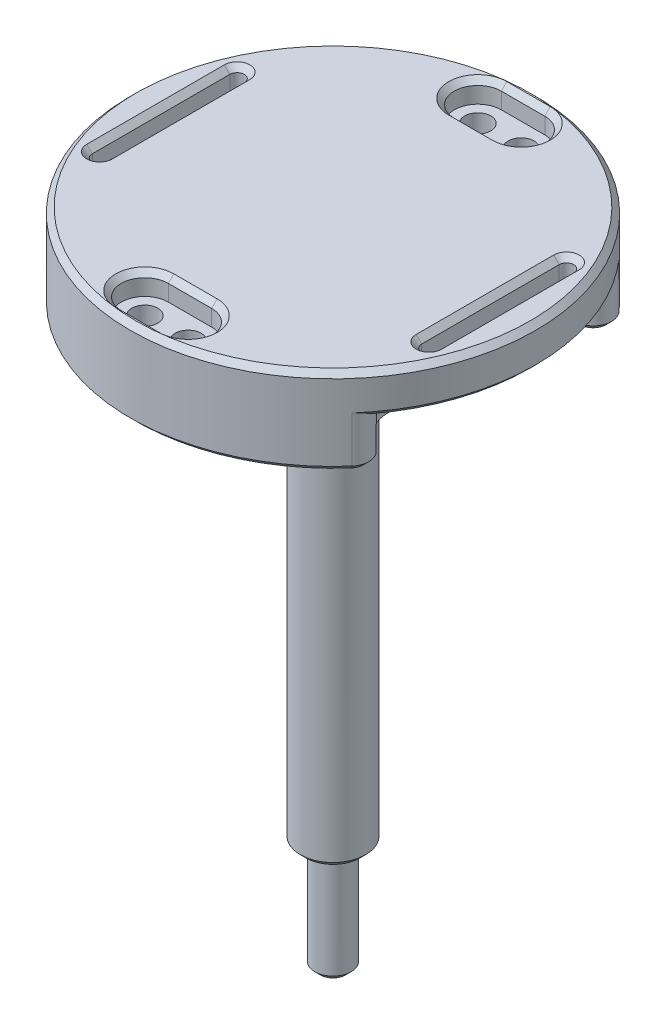
SolidWorks part; units mm, degrees
ref_plane "Front Plane" through (0, 0, 0) normal (0, 0, 1) x (1, 0, 0)
ref_plane "Top Plane" through (0, 0, 0) normal (0, 1, 0) x (1, 0, 0)
ref_plane "Right Plane" through (0, 0, 0) normal (1, 0, 0) x (0, 0, -1)
sketch "Sketch1" plane through (0, 0, 0) normal (0, 0, 1) x (1, 0, 0)
  line L0 (0, 0) -> (0, 91) construction
  line L1 (0, 91) -> (28, 91)
  line L2 (28, 91) -> (28, 79)
  line L3 (28, 79) -> (15, 79)
  line L4 (15, 79) -> (15, 80)
  line L5 (15, 80) -> (4.5, 80)
  line L6 (4.5, 80) -> (4.5, 15)
  line L7 (4.5, 15) -> (2.5, 15)
  line L8 (2.5, 15) -> (2.5, 0)
  line L9 (2.5, 0) -> (0, 0)
  line L10 (0, 0) -> (0, 91)
  dimension "D1" = 79
  dimension "D2" = 5
  dimension "D3" = 9
  dimension "D4" = 1
  dimension "D5" = 30
  dimension "D6" = 12
  dimension "D7" = 56
  dimension "D8" = 15
revolve "Revolve1" add sketch "Sketch1" angle 360 about L0
hole_wizard "CBORE for M3 SHCS1" positions "Sketch2" profile "Sketch3" counterbore size "M3" standard "ANSI Metric" end condition through all
sketch "Sketch2" plane through (0, 91, 0) normal (0, 1, 0) x (1, 0, 0)
  line L0 (0, 0) -> (0, 23) construction
  line L1 (0, 23) -> (3, 23) construction
  line L3 (0, 23) -> (-3, 23) construction
  line L5 (-3, -23) -> (0, -23) construction
  line L6 (0, -23) -> (0, 0) construction
  line L8 (0, -23) -> (3, -23) construction
  point P0 (3, 23)
  point P11 (-3, 23)
  point P14 (-3, -23)
  point P21 (3, -23)
  dimension "D1" = 46
  dimension "D2" = 6
sketch "Sketch3" plane through (3, 91, -23) normal (1, 0, 0) x (0, 0, 1)
  line L0 (0, 0) -> (0, 91)
  line L1 (0, 91) -> (1.8, 91)
  line L3 (1.8, 91) -> (1.8, 3)
  line L4 (1.8, 3) -> (3.25, 3)
  line L5 (3.25, 3) -> (3.25, 0)
  line L7 (3.25, 0) -> (0, 0)
  line L11 (0, -6.35) -> (0, 107.95) construction
  dimension "Thru Hole Dia." = 3.6
  dimension "Thru Hole Depth" = 91
  dimension "C'Bore Dia." = 6.5
  dimension "C'Bore Depth" = 3
sketch "Sketch4" plane through (0, 88, 0) normal (0, 1, 0) x (1, 0, 0)
  line L0 (-3, 23) -> (3, 23) construction
  line L1 (-3, 26.25) -> (3, 26.25)
  line L2 (-3, 19.75) -> (3, 19.75)
  line L3 (-3, -23) -> (3, -23) construction
  line L4 (-3, -19.75) -> (3, -19.75)
  line L5 (-3, -26.25) -> (3, -26.25)
  arc A0 (-3, 26.25) -> (-3, 19.75) centre (-3, 23) ccw
  arc A1 (3, 19.75) -> (3, 26.25) centre (3, 23) ccw
  arc A2 (0, 21.75) -> (0, 24.25) centre (3, 23) ccw construction
  arc A3 (-3, -19.75) -> (-3, -26.25) centre (-3, -23) ccw
  arc A4 (3, -26.25) -> (3, -19.75) centre (3, -23) ccw
  arc A5 (0, -21.75) -> (0, -24.25) centre (-3, -23) ccw construction
  point P4 (0, 23)
  point P16 (0, -23)
extrude "Cut-Extrude1" cut sketch "Sketch4" along normal through all
sketch "Sketch5" plane through (0, 91, 0) normal (0, 1, 0) x (1, 0, 0)
  line L0 (-22.75, -9.5) -> (-22.75, 9.5) construction
  line L1 (-23.75, -9.5) -> (-23.75, 9.5)
  line L2 (-21.75, -9.5) -> (-21.75, 9.5)
  arc A0 (-23.75, -9.5) -> (-21.75, -9.5) centre (-22.75, -9.5) ccw
  arc A1 (-21.75, 9.5) -> (-23.75, 9.5) centre (-22.75, 9.5) ccw
  point P2 (-22.75, 0)
  dimension "D1" = 22.75
  dimension "D2" = 19
  dimension "D3" = 2
extrude "Cut-Extrude2" cut sketch "Sketch5" against normal through all
mirror "Mirror1" about plane through (0, 0, 0) normal (1, 0, 0) of "Cut-Extrude2"
sketch "Sketch7" plane through (0, 79, 0) normal (0, -1, 0) x (1, 0, 0)
  line L0 (21.75, -9.5) -> (21.75, 9.5)
  line L1 (21.75, -9.5) -> (21.75, 9.5) construction
  line L2 (23.75, 9.5) -> (23.75, -9.5)
  line L3 (23.75, 9.5) -> (23.75, -9.5) construction
  line L4 (-21.75, -9.5) -> (-21.75, 9.5)
  line L5 (-21.75, -9.5) -> (-21.75, 9.5) construction
  line L6 (-23.75, 9.5) -> (-23.75, -9.5)
  line L7 (-23.75, 9.5) -> (-23.75, -9.5) construction
  line L8 (28.322, 9.5) -> (28.322, -9.5)
  line L9 (17.178, -9.5) -> (17.178, 9.5)
  line L10 (-17.178, -9.5) -> (-17.178, 9.5)
  line L11 (-28.322, 9.5) -> (-28.322, -9.5)
  arc A0 (23.75, 9.5) -> (21.75, 9.5) centre (22.75, 9.5) ccw
  arc A1 (23.75, 9.5) -> (21.75, 9.5) centre (22.75, 9.5) ccw construction
  arc A2 (21.75, -9.5) -> (23.75, -9.5) centre (22.75, -9.5) ccw
  arc A3 (21.75, -9.5) -> (23.75, -9.5) centre (22.75, -9.5) ccw construction
  arc A4 (-23.75, -9.5) -> (-21.75, -9.5) centre (-22.75, -9.5) ccw
  arc A5 (-23.75, -9.5) -> (-21.75, -9.5) centre (-22.75, -9.5) ccw construction
  arc A6 (-21.75, 9.5) -> (-23.75, 9.5) centre (-22.75, 9.5) ccw
  arc A7 (-21.75, 9.5) -> (-23.75, 9.5) centre (-22.75, 9.5) ccw construction
  arc A8 (17.178, -9.5) -> (28.322, -9.5) centre (22.75, -9.5) ccw
  arc A9 (28.322, 9.5) -> (17.178, 9.5) centre (22.75, 9.5) ccw
  arc A10 (-17.178, 9.5) -> (-28.322, 9.5) centre (-22.75, 9.5) ccw
  arc A11 (-28.322, -9.5) -> (-17.178, -9.5) centre (-22.75, -9.5) ccw
  dimension "D1" = 4.572
  dimension "D2" = 4.572
extrude "Cut-Extrude3" cut sketch "Sketch7" against normal blind 6.35
fillet "Fillet1" radius 2.54 4 edges at (23.6432, 82.175, 14.9999) (23.6432, 82.175, -14.9999) (-23.6432, 82.175, -14.9999) (-23.6432, 82.175, 14.9999)
fillet "Fillet2" radius 1.27 8 edges at (-22.75, 85.35, -10.5) (-21.75, 85.35, 0) (-22.75, 85.35, 10.5) (22.75, 85.35, 10.5) (23.75, 85.35, 0) (22.75, 85.35, -10.5) (-23.75, 85.35, 0) (21.75, 85.35, 0)
chamfer "Chamfer1" distance 0.762 angle 45 38 edges at (0, 79, -15) (3, 79, 21.2) (-3, 79, 21.2) (-3, 79, -24.8) (3, 79, -24.8) (22.75, 91, -10.5) (21.75, 91, 0) (22.75, 91, 10.5) (23.75, 91, 0) (0, 91, -26.25) (-6.25, 91, -23) (0, 91, -19.75) (6.25, 91, -23) (0, 91, 19.75) (-6.25, 91, 23) (0, 91, 26.25) (6.25, 91, 23) (0, 91, -28) (-21.75, 91, 0) (-22.75, 91, -10.5) (-23.75, 91, 0) (-22.75, 91, 10.5) (0, 15, -4.5) (0, 0, -2.5) (17.178, 79, 0) (18.0168, 79, -12.4401) (21.6463, 79, -16.2766) (0, 79, -28) (-21.6463, 79, -16.2766) (-18.0168, 79, -12.4401) (-17.178, 79, 0) (-18.0168, 79, 12.4401) (-21.6463, 79, 16.2766) (0, 79, 28) (21.6463, 79, 16.2766) (18.0168, 79, 12.4401) (-28, 85.35, 0) (28, 85.35, 0)
fillet "Fillet3" radius 2.54 1 edges at (0, 80, -4.5)
equation "\"mm\"=0.1"
